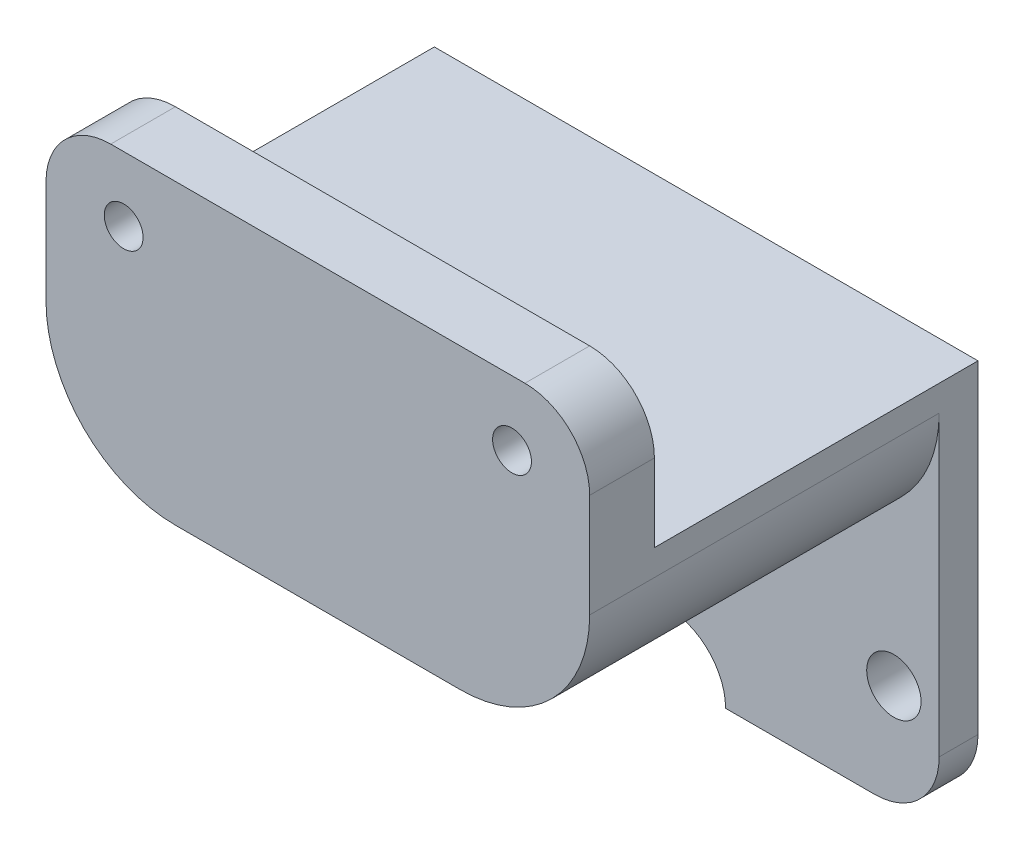
SolidWorks part; units mm, degrees
ref_plane "Front Plane" through (0, 0, 0) normal (0, 0, 1) x (1, 0, 0)
ref_plane "Top Plane" through (0, 0, 0) normal (0, 1, 0) x (1, 0, 0)
ref_plane "Right Plane" through (0, 0, 0) normal (1, 0, 0) x (0, 0, -1)
sketch "Sketch3" plane through (0, 0, 0) normal (0, 0, 1) x (1, 0, 0)
  line L0 (-22.5928, 16.5094) -> (-6.0928, 16.5094)
  line L1 (-48.0928, 16.5094) -> (-31.5928, 16.5094)
  line L2 (-48.0928, 16.5094) -> (-48.0928, 3.5094)
  line L3 (-38.0928, -6.4906) -> (-16.0928, -6.4906)
  line L4 (-6.0928, 16.5094) -> (-6.0928, 3.5094)
  line L5 (-31.5928, 16.5094) -> (-22.5928, 16.5094)
  circle A1 centre (-42.0928, 11.5094) radius 1.5
  circle A2 centre (-12.0928, 11.5094) radius 1.5
  arc A3 (-48.0928, 3.5094) -> (-38.0928, -6.4906) centre (-38.0928, 3.5094) ccw
  arc A4 (-16.0928, -6.4906) -> (-6.0928, 3.5094) centre (-16.0928, 3.5094) ccw
  point P12 (-27.0928, -6.4906)
  point P16 (-48.0928, -6.4906)
  dimension "D4" = 3
  dimension "D5" = 3
  dimension "D12" = 10
  dimension "D13" = 10
  dimension "D1" = 42
  dimension "D2" = 23
  dimension "D6" = 18
  dimension "D7" = 30
  dimension "D8" = 18
  dimension "D9" = 15
  dimension "D10" = 15
extrude "Boss-Extrude3" add sketch "Sketch3" along normal blind 5
sketch "Sketch6" plane through (0, 0, 0) normal (0, 0, 1) x (1, 0, 0)
  line L2 (-48.0928, 5.5094) -> (-48.0928, 3.5094)
  line L3 (-38.0928, -6.4906) -> (-16.0928, -6.4906)
  line L4 (-6.0928, 5.5094) -> (-6.0928, 3.5094)
  line L5 (-6.0928, 5.5094) -> (-48.0928, 5.5094)
  arc A3 (-48.0928, 3.5094) -> (-38.0928, -6.4906) centre (-38.0928, 3.5094) ccw
  arc A4 (-16.0928, -6.4906) -> (-6.0928, 3.5094) centre (-16.0928, 3.5094) ccw
  dimension "D1" = 12
extrude "Boss-Extrude4" add sketch "Sketch6" against normal blind 25
ref_plane "Plane7" through (0, 5.5094, 0) normal (0, 1, 0) x (1, 0, 0)
sketch "Sketch9" plane through (0, 5.5094, 0) normal (0, 1, 0) x (1, 0, 0)
  line L0 (-48.0928, 25) -> (-48.0928, 0) construction
  line L1 (-6.0928, 25) -> (-48.0928, 25)
  line L2 (-6.0928, 25) -> (-6.0928, 22)
  line L3 (-6.0928, 22) -> (-48.0928, 22)
  line L4 (-48.0928, 25) -> (-48.0928, 22)
  dimension "D1" = 42
  dimension "D2" = 3
fillet "Fillet4" radius 5 2 edges at (-48.0928, 16.5094, 2.5) (-6.0928, 16.5094, 2.5)
extrude "Boss-Extrude7" add sketch "Sketch9" against normal blind 30
fillet "Fillet6" radius 5 1 edges at (-6.0928, -24.4906, -23.5)
fillet "Fillet7" radius 5 1 edges at (-48.0928, -24.4906, -23.5)
ref_plane "Plane13" through (0, 0, -25) normal (0, 0, -1) x (-1, 0, 0)
sketch "Sketch11" plane through (0, 0, -25) normal (0, 0, -1) x (-1, 0, 0)
  line L0 (6.0928, -19.4906) -> (6.0928, 5.5094) construction
  line L3 (22.5928, -24.4906) -> (31.5928, -24.4906)
  line L4 (48.0928, 5.5094) -> (48.0928, -19.4906) construction
  arc A0 (31.5928, -24.4906) -> (22.5928, -24.4906) centre (27.0928, -24.4906) ccw
  circle A1 centre (9.5928, -16.4906) radius 2.1
  circle A2 centre (44.5928, -16.4906) radius 2.1
  dimension "D4" = 8
  dimension "D1" = 4.2
  dimension "D2" = 35
  dimension "D3" = 17.5
  dimension "D5" = 8
  dimension "D6" = 17.5
  dimension "D7" = 21
  dimension "D8" = 21
  dimension "D9" = 3.5
  dimension "D10" = 3.5
extrude "Cut-Extrude2" cut sketch "Sketch11" against normal blind 30
